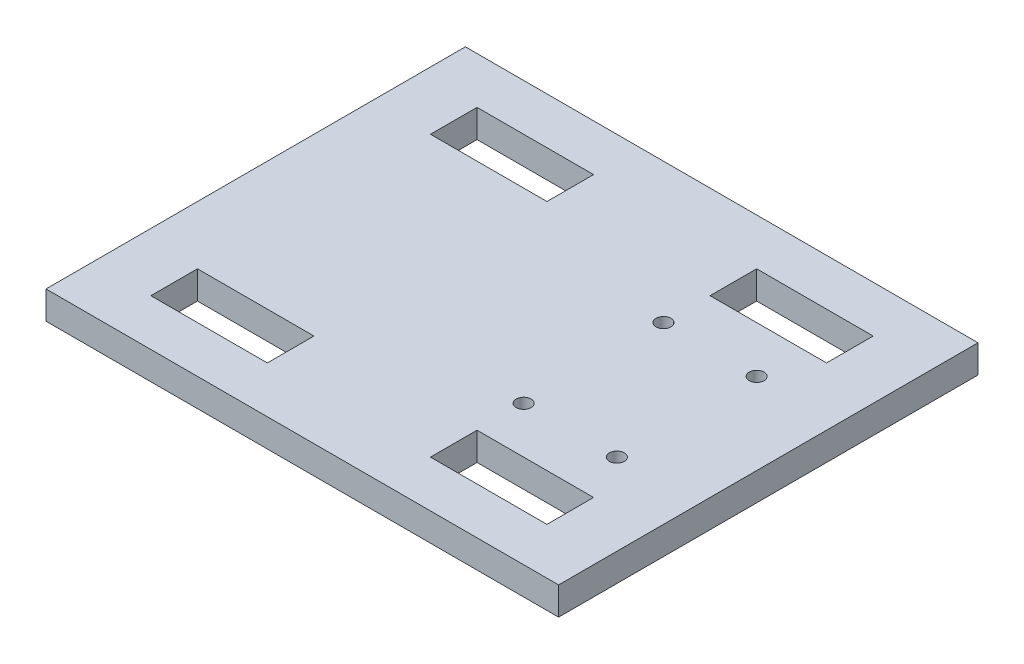
SolidWorks part; units mm, degrees
material "Maple"
ref_plane "Front Plane" through (0, 0, 0) normal (0, 0, 1) x (1, 0, 0)
ref_plane "Top Plane" through (0, 0, 0) normal (0, 1, 0) x (1, 0, 0)
ref_plane "Right Plane" through (0, 0, 0) normal (1, 0, 0) x (0, 0, -1)
sketch "Sketch1" plane through (0, 0, 0) normal (0, 1, 0) x (1, 0, 0)
  line L0 (-55, 0) -> (55, 0) construction
  line L1 (-55, 45) -> (55, 45)
  line L2 (-55, 45) -> (-55, -45)
  line L3 (-55, -45) -> (55, -45)
  line L4 (55, 45) -> (55, -45)
  point P0 (0, 0)
  dimension "D1" = 90
  dimension "D2" = 110
extrude "Boss-Extrude1" add sketch "Sketch1" along normal blind 6
sketch "Sketch2" plane through (0, 6, 0) normal (0, 1, 0) x (1, 0, 0)
  line L0 (-55, 0) -> (55, 0) construction
  line L1 (-55, 45) -> (-55, -45) construction
  line L2 (55, -45) -> (55, 45) construction
  line L3 (0, 0) -> (0, 45) construction
  line L4 (17.5, 35) -> (42.5, 35)
  line L5 (17.5, 35) -> (17.5, 25)
  line L6 (17.5, 25) -> (42.5, 25)
  line L7 (42.5, 35) -> (42.5, 25)
  line L8 (17.5, 35) -> (42.5, 25) construction
  line L9 (17.5, 25) -> (42.5, 35) construction
  line L10 (55, 45) -> (-55, 45) construction
  point P6 (30, 30)
  dimension "D1" = 10
  dimension "D2" = 60
  dimension "D3" = 60
  dimension "D4" = 25
extrude "Cut-Extrude1" cut sketch "Sketch2" against normal through all
mirror "Mirror1" about plane through (0, 0, 0) normal (0, 0, 1) of "Cut-Extrude1"
mirror "Mirror2" about plane through (0, 0, 0) normal (1, 0, 0) of "Mirror1", "Cut-Extrude1"
hole_wizard "M3 Clearance Hole1" positions "Sketch4" profile "Sketch3" hole size "M3" standard "ANSI Metric" end condition through all
sketch "Sketch4" plane through (0, 6, 0) normal (0, 1, 0) x (1, 0, 0)
  line L0 (13.7067, -15) -> (41.2933, -15) construction
  line L1 (13.7067, 15) -> (41.2933, 15) construction
  line L3 (17.5, 15) -> (17.5, -15) construction
  line L5 (37.5, 15) -> (37.5, -15) construction
  line L7 (27.5, 15) -> (27.5, -15) construction
  point P0 (17.5, 15)
  point P2 (37.5, 15)
  point P4 (17.5, -15)
  point P6 (37.5, -15)
  dimension "D2" = 20
sketch "Sketch3" plane through (17.5, 6, -15) normal (1, 0, 0) x (0, 0, 1)
  line L0 (0, 0) -> (0, 6)
  line L1 (0, 6) -> (1.6, 6)
  line L2 (1.6, 6) -> (1.6, 0)
  line L5 (1.6, 0) -> (0, 0)
  line L11 (0, -6.35) -> (0, 107.95) construction
  dimension "Thru Hole Dia." = 3.2
  dimension "Thru Hole Depth" = 6
